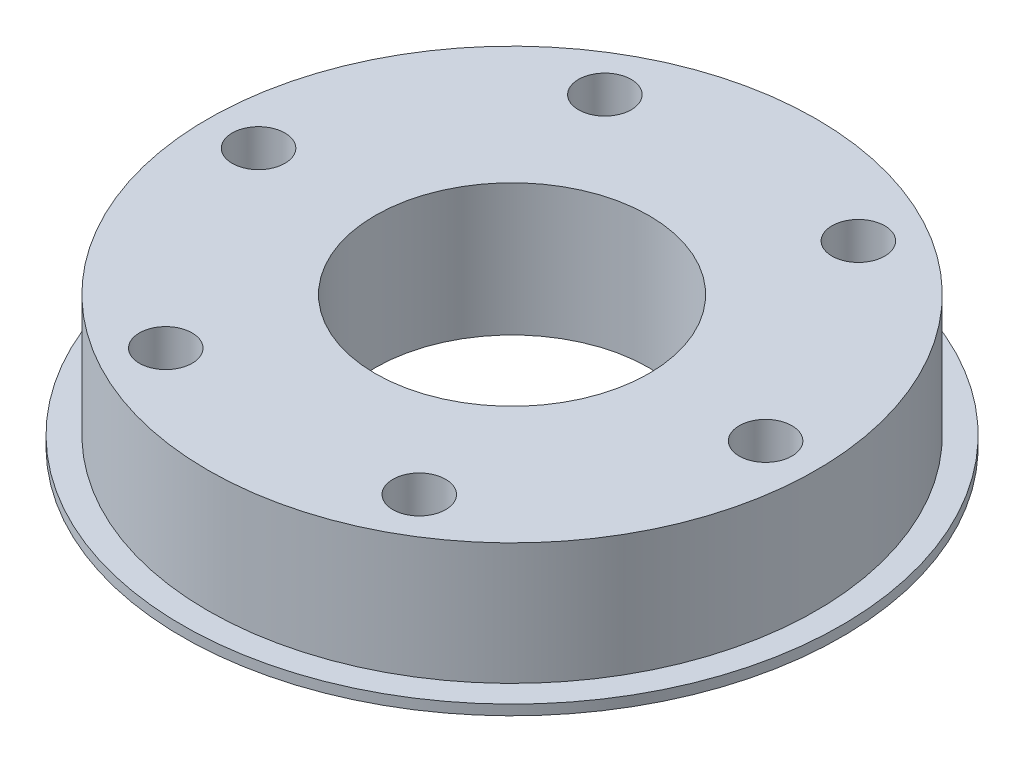
SolidWorks part; units mm, degrees
ref_plane "Front Plane" through (0, 0, 0) normal (0, 0, 1) x (1, 0, 0)
ref_plane "Top Plane" through (0, 0, 0) normal (0, 1, 0) x (1, 0, 0)
ref_plane "Right Plane" through (0, 0, 0) normal (1, 0, 0) x (0, 0, -1)
sketch "Sketch1" plane through (0, 0, 0) normal (0, 1, 0) x (1, 0, 0)
  circle A0 centre (0, 0) radius 30
  point P18 (0, 0)
  dimension "D4" = 60
extrude "Boss-Extrude1" add sketch "Sketch1" along normal blind 13
sketch "Sketch2" plane through (0, 0, 0) normal (0, -1, 0) x (1, 0, 0)
  circle A0 centre (0, 0) radius 32.5
  dimension "D1" = 65
extrude "Boss-Extrude2" add sketch "Sketch2" against normal blind 1
sketch "Sketch3" plane through (0, 0, 0) normal (0, 1, 0) x (1, 0, 0)
  circle A1 centre (0, 0) radius 25 construction
  circle A2 centre (0, 25) radius 1.6
  circle A3 centre (21.6506, 12.5) radius 1.6
  circle A4 centre (21.6506, -12.5) radius 1.6
  circle A5 centre (0, -25) radius 1.6
  circle A6 centre (-21.6506, -12.5) radius 1.6
  circle A7 centre (-21.6506, 12.5) radius 1.6
  point P30 (0, 0)
  dimension "D1" = 50
  dimension "D2" = 3.2
  dimension "D3" = 6
extrude "Cut-Extrude1" cut sketch "Sketch3" along normal blind 3.5
sketch "Sketch4" plane through (0, 0, 0) normal (0, -1, 0) x (1, 0, 0)
  circle A0 centre (0, 0) radius 13.5
  dimension "D1" = 27
extrude "Cut-Extrude2" cut sketch "Sketch4" against normal blind 51
sketch "Sketch5" plane through (0, 0, 0) normal (0, -1, 0) x (1, 0, 0)
  line L0 (-12.5, 21.6506) -> (0, 0) construction
  line L1 (0, 0) -> (0, 25) construction
  line L2 (0, 25) -> (-21.6506, 12.5) construction
  circle A0 centre (0, 0) radius 25 construction
  circle A1 centre (-12.5, 21.6506) radius 2.6
  circle A2 centre (12.5, 21.6506) radius 2.6
  circle A3 centre (25, 0) radius 2.6
  circle A4 centre (12.5, -21.6506) radius 2.6
  circle A5 centre (-12.5, -21.6506) radius 2.6
  circle A6 centre (-25, 0) radius 2.6
  point P21 (0, 0)
  dimension "D1" = 5.2
  dimension "D2" = 6
extrude "Cut-Extrude3" cut sketch "Sketch5" against normal blind 25
